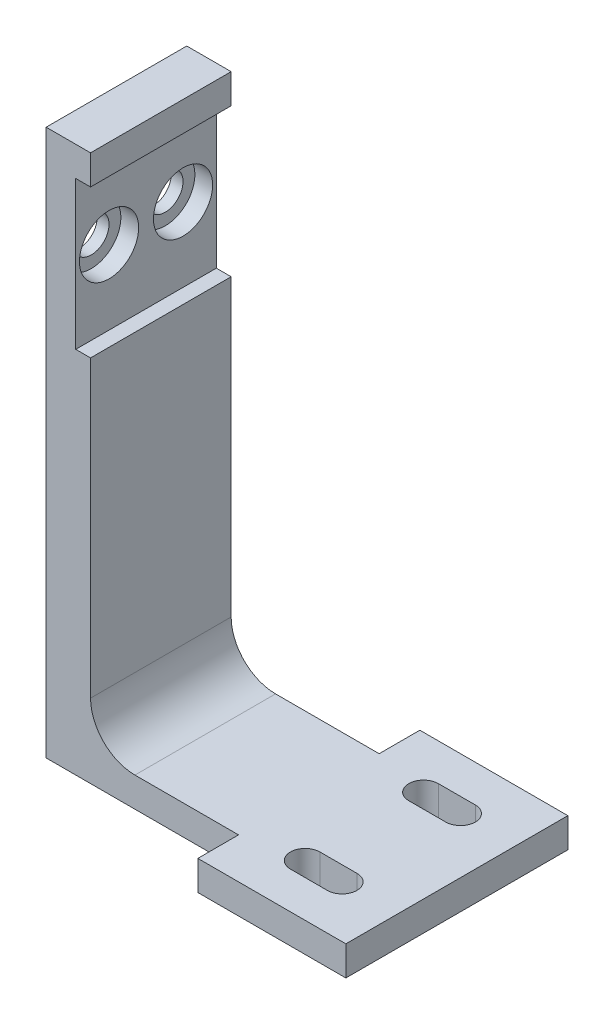
SolidWorks part; units mm, degrees
material "6061-T6 (SS)"
ref_plane "Front Plane" through (0, 0, 0) normal (0, 0, 1) x (1, 0, 0)
ref_plane "Top Plane" through (0, 0, 0) normal (0, 1, 0) x (1, 0, 0)
ref_plane "Right Plane" through (0, 0, 0) normal (1, 0, 0) x (0, 0, -1)
sketch "Sketch1" plane through (0, 0, 0) normal (0, 0, 1) x (1, 0, 0)
  line L0 (-15.4886, 21.8) -> (-17.5374, 21.8) construction
  line L9 (-17.5374, 16.8) -> (-17.5374, 26.8)
  line L10 (-19.5374, 0) -> (-19.5374, 28.8)
  line L11 (-19.5374, 28.8) -> (-16.5374, 28.8)
  line L12 (-16.5374, 28.8) -> (-16.5374, 26.8)
  line L17 (-12.4274, -6.11) -> (3.4626, -6.11)
  line L18 (3.4626, -6.11) -> (3.4626, -8.11)
  line L19 (3.4626, -8.11) -> (-11.4274, -8.11)
  line L20 (-17.5374, 26.8) -> (-16.5374, 26.8)
  line L21 (-17.5374, 16.8) -> (-16.5374, 16.8)
  line L22 (-16.5374, 16.8) -> (-16.5374, 13.8)
  line L23 (-19.5374, 0) -> (-19.5374, -8.11)
  line L24 (-19.5374, -8.11) -> (-11.4274, -8.11)
  line L25 (-16.5374, 13.8) -> (-16.5374, -6.11)
  line L26 (-16.5374, -6.11) -> (-12.4274, -6.11)
  line L29 (-12.4274, -6.11) -> (-10.0144, -6.11) construction
  point P15 (-17.5374, 21.8)
  point P21 (-12.4274, 0)
  dimension "D3" = 36.91
  dimension "D4" = 3
  dimension "D2" = 3
  dimension "D5" = 23
  dimension "D6" = 10
  dimension "D7" = 2
  dimension "D8" = 1
  dimension "D10" = 2
extrude "Boss-Extrude1" add sketch "Sketch1" along normal mid plane 9.5
sketch "Sketch2" plane through (-17.5374, 0, 0) normal (1, 0, 0) x (0, 0, -1)
  line L0 (-4.75, 21.8) -> (4.75, 21.8) construction
  line L1 (-4.75, 16.8) -> (-4.75, 26.8) construction
  line L2 (4.75, 16.8) -> (4.75, 26.8) construction
  point P8 (-2.5, 21.8)
  point P9 (0, 21.8)
  point P11 (2.5, 21.8)
  dimension "D2" = 2.5
  dimension "D1" = 2.5
hole_wizard "M2 Clearance Hole1" positions "3DSketch1" profile "Sketch3" hole size "M2" standard "ANSI Metric" end condition through all
sketch3d "3DSketch1"
  point P0 (-17.5374, 21.8, 2.5)
  point P3 (-17.5374, 21.8, -2.5)
sketch "Sketch3" plane through (-17.5374, 21.8, 2.5) normal (0, 1, 0) x (0, 0, -1)
  line L0 (0, 0) -> (0, 2)
  line L1 (0, 2) -> (1.2, 2)
  line L2 (1.2, 2) -> (1.2, 0)
  line L5 (1.2, 0) -> (0, 0)
  line L11 (0, -6.35) -> (0, 107.95) construction
  dimension "Thru Hole Dia." = 2.4
  dimension "Thru Hole Depth" = 2
sketch "Sketch4" plane through (-17.5374, 0, 0) normal (1, 0, 0) x (0, 0, -1)
  circle A0 centre (-2.5, 21.8) radius 2
  circle A1 centre (2.5, 21.8) radius 2
  dimension "D1" = 4
  dimension "D2" = 4
extrude "Cut-Extrude1" cut sketch "Sketch4" against normal blind 1.2
sketch "Sketch5" plane through (0, -8.11, 0) normal (0, -1, 0) x (1, 0, 0)
  line L0 (3.4626, -7.5) -> (3.4626, 7.5)
  line L1 (3.4626, 4.75) -> (3.4626, -4.75) construction
  line L2 (3.4626, 7.5) -> (-6.5374, 7.5)
  line L3 (-6.5374, 7.5) -> (-6.5374, -7.5)
  line L4 (-6.5374, -7.5) -> (3.4626, -7.5)
  point P3 (3.4626, 0)
  dimension "D1" = 10
  dimension "D2" = 15
extrude "Boss-Extrude2" add sketch "Sketch5" against normal blind 2
sketch "Sketch6" plane through (0, -6.11, 0) normal (0, 1, 0) x (1, 0, 0)
  line L0 (3.4626, 0) -> (-6.5374, 0) construction
  line L1 (3.4626, 7.5) -> (3.4626, -7.5) construction
  line L2 (-0.2874, -4) -> (-2.7874, -4) construction
  line L3 (-1.5374, -7.5) -> (-1.5374, 7.5) construction
  line L4 (3.4626, -7.5) -> (-6.5374, -7.5) construction
  line L5 (-6.5374, 7.5) -> (3.4626, 7.5) construction
  line L6 (-0.2874, -5) -> (-2.7874, -5)
  line L7 (-0.2874, -3) -> (-2.7874, -3)
  line L8 (-0.2874, 4) -> (-2.7874, 4) construction
  line L9 (-0.2874, 5) -> (-2.7874, 5)
  line L10 (-0.2874, 3) -> (-2.7874, 3)
  arc A0 (-0.2874, -5) -> (-0.2874, -3) centre (-0.2874, -4) ccw
  arc A1 (-2.7874, -3) -> (-2.7874, -5) centre (-2.7874, -4) ccw
  arc A2 (-0.2874, 5) -> (-0.2874, 3) centre (-0.2874, 4) cw
  arc A3 (-2.7874, 3) -> (-2.7874, 5) centre (-2.7874, 4) cw
  point P12 (-1.5374, -4)
  point P13 (-1.5374, 0)
  point P14 (-1.5374, 4)
  point P15 (-1.5374, -4)
  point P23 (-1.5374, 4)
  dimension "D3" = 1
  dimension "D1" = 4
  dimension "D2" = 2.5
extrude "Cut-Extrude2" cut sketch "Sketch6" against normal up to surface (2 mm away) up to face at (-7.2874, -8.11, 0)
fillet "Fillet1" radius 3 1 edges at (-16.5374, -6.11, 0)
